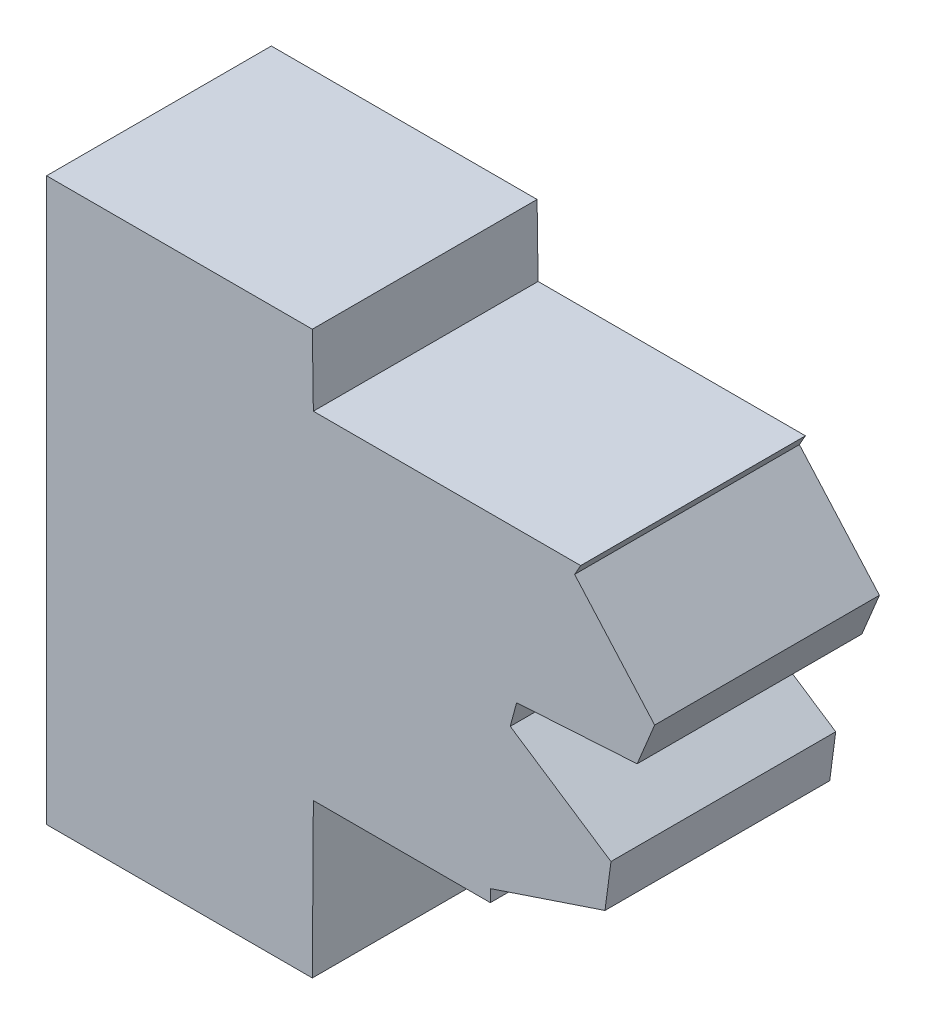
SolidWorks part; units mm, degrees
ref_plane "Front Plane" through (0, 0, 0) normal (0, 0, 1) x (1, 0, 0)
ref_plane "Top Plane" through (0, 0, 0) normal (0, 1, 0) x (1, 0, 0)
ref_plane "Right Plane" through (0, 0, 0) normal (1, 0, 0) x (0, 0, -1)
sketch "Sketch1" plane through (0, 0, 0) normal (0, 0, 1) x (1, 0, 0)
  line L0 (0.0178, 2.7448) -> (3.1678, 2.7448)
  line L1 (0.0178, 2.7448) -> (0, 0)
  line L2 (0.0178, 8.7448) -> (4.7755, 8.7448)
  line L3 (3.1678, 2.7448) -> (3.1698, 2.9629)
  line L4 (0, 0) -> (-4.73, 0)
  line L5 (3.1698, 2.9629) -> (5.2084, 3.6448)
  line L6 (5.2084, 3.6448) -> (5.3148, 4.4531)
  line L7 (5.3148, 4.4531) -> (3.5221, 5.6394)
  line L8 (3.5221, 5.6394) -> (3.635, 6.0607)
  line L9 (3.635, 6.0607) -> (5.7807, 6.1918)
  line L10 (5.7807, 6.1918) -> (6.0927, 6.9451)
  line L11 (6.0927, 6.9451) -> (4.6682, 8.5549)
  line L12 (4.6682, 8.5549) -> (4.7755, 8.7448)
  line L13 (0, 10) -> (-4.73, 10)
  line L14 (-4.73, 0) -> (-4.73, 10)
  line L15 (0, 10) -> (0.0178, 8.7448)
  dimension "D1" = 0.8153
  dimension "D2" = 2.1496
  dimension "D3" = 0.2181
  dimension "D4" = 0.2181
  dimension "D5" = 2.1496
  dimension "D6" = 2.1496
  dimension "D7" = 0.8153
  dimension "D8" = 2.1496
  dimension "D9" = 6
  dimension "D10" = 4.7577
  dimension "D11" = 3.15
  dimension "D12" = 10
  dimension "D13" = 4.73
  dimension "D14" = 1.2552
  dimension "D15" = 2.7448
extrude "Boss-Extrude1" add sketch "Sketch1" along normal blind 4
